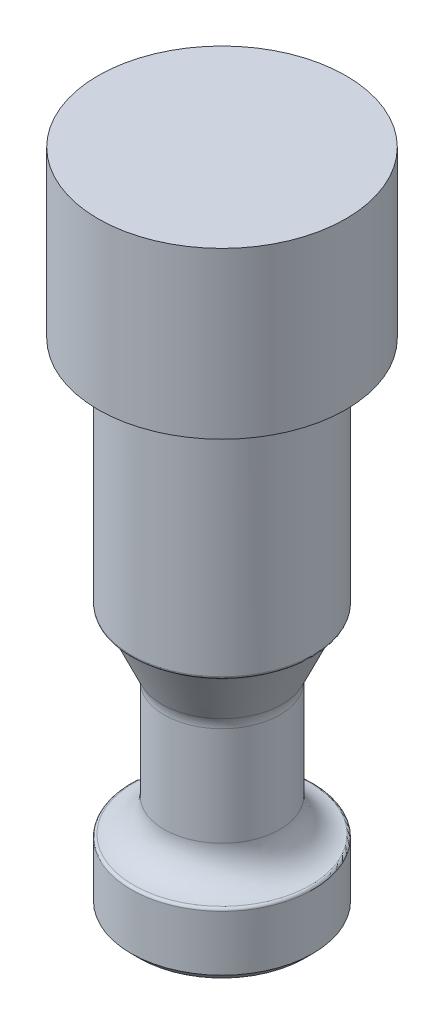
SolidWorks part; units mm, degrees
ref_plane "Front Plane" through (0, 0, 0) normal (0, 0, 1) x (1, 0, 0)
ref_plane "Top Plane" through (0, 0, 0) normal (0, 1, 0) x (1, 0, 0)
ref_plane "Right Plane" through (0, 0, 0) normal (1, 0, 0) x (0, 0, -1)
sketch "Sketch1" plane through (0, 0, 0) normal (0, 1, 0) x (1, 0, 0)
  circle A0 centre (0, 0) radius 8.7312
  dimension "D1" = 17.4625
extrude "main" add sketch "Sketch1" along normal blind 47.625
chamfer "Chamfer1" distance 0.7937 1 edges at (0, 0, 8.7312)
sketch "Sketch2" plane through (0, 0, 0) normal (1, 0, 0) x (0, 0, -1)
  line L0 (8.7312, 0.7938) -> (8.7312, 47.625) construction
  line L1 (-8.7312, 47.625) -> (-8.7312, 0.7938) construction
  line L2 (8.7312, 47.625) -> (-8.7312, 47.625) construction
  line L3 (8.7312, 0.7938) -> (8.7312, 47.625)
  line L4 (-8.7312, 47.625) -> (-8.7312, 0.7938)
  line L5 (8.7312, 47.625) -> (-8.7312, 47.625)
  line L12 (-7.9375, 0) -> (7.9375, 0) construction
  line L13 (-5.5562, 19.05) -> (-5.5562, 9.525)
  line L14 (-8.7312, 25.4) -> (-8.7312, 6.35)
  line L15 (-5.7717, 20.0398) -> (-8.0093, 24.9362)
  arc A5 (-8.7312, 25.4) -> (-8.0093, 24.9362) centre (-8.7312, 24.6063) cw
  arc A6 (-5.5562, 19.05) -> (-5.7717, 20.0398) centre (-7.9375, 19.05) ccw
  arc A7 (-8.7312, 6.35) -> (-5.5562, 9.525) centre (-8.7312, 9.525) ccw
  dimension "D4" = 2.3812
  dimension "D6" = 19.05
  dimension "D1" = 0.7938
  dimension "D2" = 3.175
  dimension "D3" = 6.35
  dimension "D7" = 3.175
  dimension "D8" = 6.35
ref_axis "Axis1" through (0, 47.625, 0) along (0, -1, 0)
revolve "ball_channel" cut sketch "Sketch2" angle 360 about axis through (0, 47.625, 0) along (0, -1, 0) region at (0, 15.0761, 7.2886)
fillet "Fillet1" radius 0.254 2 edges at (0, 25.4, 8.7312) (0, 6.35, 8.7312)
sketch "Sketch6" plane through (0, 47.625, 0) normal (0, 1, 0) x (1, 0, 0)
  circle A0 centre (0, 0) radius 11.9062
  dimension "D1" = 23.8125
extrude "spring_stabilizer" add sketch "Sketch6" along normal blind 15.875
